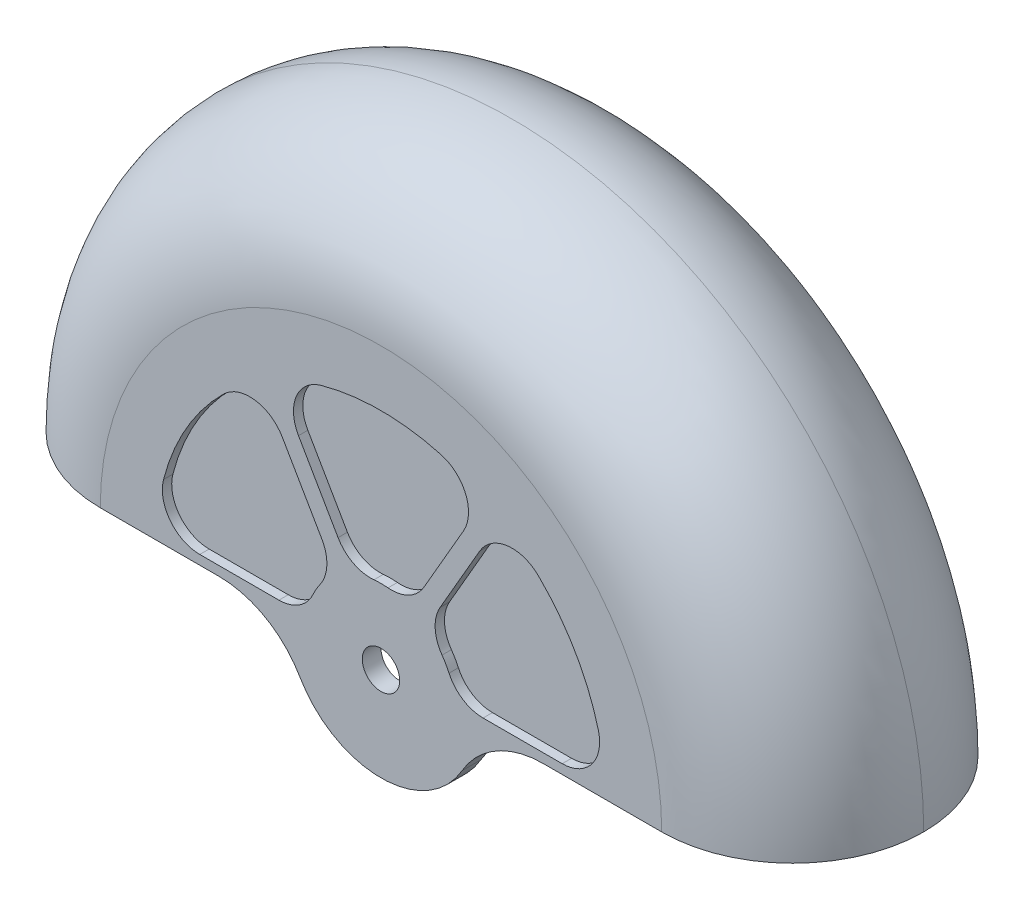
SolidWorks part; units mm, degrees
ref_plane "Front Plane" through (0, 0, 0) normal (0, 0, 1) x (1, 0, 0)
ref_plane "Top Plane" through (0, 0, 0) normal (0, 1, 0) x (1, 0, 0)
ref_plane "Right Plane" through (0, 0, 0) normal (1, 0, 0) x (0, 0, -1)
sketch "Sketch1" plane through (0, 0, 0) normal (0, 0, 1) x (1, 0, 0)
  circle A0 centre (0, 0) radius 110
  dimension "D1" = 220
extrude "Extrude1" add sketch "Sketch1" along normal blind 70
fillet "Fillet1" radius 35 2 edges at (110, 0, 0) (110, 0, 70)
sketch "Sketch2" plane through (0, 0, 0) normal (0, 0, 1) x (1, 0, 0)
  line L0 (43.3013, 0) -> (110, 0)
  line L1 (-110, 0) -> (-43.3013, 0)
  line L2 (-110, 0) -> (-110, -110)
  line L3 (-110, -110) -> (110, -110)
  line L4 (110, 0) -> (110, -110)
  arc A0 (-21.6506, -12.5) -> (21.6506, -12.5) centre (0, 0) ccw
  circle A1 centre (0, 0) radius 110 construction
  arc A2 (-43.3013, 0) -> (-21.6506, -12.5) centre (-43.3013, -25) cw
  arc A3 (43.3013, 0) -> (21.6506, -12.5) centre (43.3013, -25) ccw
  dimension "D1" = 50
  dimension "D2" = 25
extrude "Extrude2" cut sketch "Sketch2" along normal through all
shell "Shell1" thickness 5 removed face at (-72.22, 0, 35) removed face at (-31.6386, -4.7997, 35) removed face at (0, -18.75, 35) removed face at (31.6386, -4.7997, 35) removed face at (72.22, 0, 35)
sketch "Sketch3" plane through (0, 0, 70) normal (0, 0, 1) x (1, 0, 0)
  circle A0 centre (0, 0) radius 5
  dimension "D1" = 10
extrude "Extrude3" cut sketch "Sketch3" against normal through all
sketch "Sketch5" plane through (0, 0, 70) normal (0, 0, 1) x (1, 0, 0)
  line L3 (-27.2718, 2.5) -> (-48.4123, 2.5)
  line L4 (-11.4708, 24.8681) -> (-22.0411, 43.1763)
  line L5 (27.2718, 2.5) -> (48.4123, 2.5)
  line L8 (-15.801, 22.3681) -> (-26.3712, 40.6763)
  line L9 (11.4708, 24.8681) -> (22.0411, 43.1763)
  line L10 (15.801, 22.3681) -> (26.3712, 40.6763)
  arc A0 (58.0948, 15) -> (42.0378, 42.8115) centre (0, 0) ccw
  arc A1 (18.1812, 8.3333) -> (16.3075, 11.5787) centre (0, 0) ccw
  arc A2 (16.057, 57.8115) -> (-16.057, 57.8115) centre (0, 0) ccw
  arc A3 (1.8737, 19.912) -> (-1.8737, 19.912) centre (0, 0) ccw
  arc A4 (-16.3075, 11.5787) -> (-18.1812, 8.3333) centre (0, 0) ccw
  arc A5 (-27.2718, 2.5) -> (-18.1812, 8.3333) centre (-27.2718, 12.5) ccw
  arc A6 (-42.0378, 42.8115) -> (-58.0948, 15) centre (0, 0) ccw
  arc A7 (-15.801, 22.3681) -> (-16.3075, 11.5787) centre (-24.4612, 17.3681) cw
  arc A8 (-11.4708, 24.8681) -> (-1.8737, 19.912) centre (-2.8106, 29.8681) ccw
  arc A9 (11.4708, 24.8681) -> (1.8737, 19.912) centre (2.8106, 29.8681) cw
  arc A10 (-22.0411, 43.1763) -> (-16.057, 57.8115) centre (-13.3808, 48.1763) cw
  arc A11 (-42.0378, 42.8115) -> (-26.3712, 40.6763) centre (-35.0315, 35.6763) cw
  arc A12 (16.057, 57.8115) -> (22.0411, 43.1763) centre (13.3808, 48.1763) cw
  arc A13 (42.0378, 42.8115) -> (26.3712, 40.6763) centre (35.0315, 35.6763) ccw
  arc A14 (15.801, 22.3681) -> (16.3075, 11.5787) centre (24.4612, 17.3681) ccw
  arc A15 (27.2718, 2.5) -> (18.1812, 8.3333) centre (27.2718, 12.5) cw
  arc A16 (48.4123, 2.5) -> (58.0948, 15) centre (48.4123, 12.5) ccw
  arc A17 (-48.4123, 2.5) -> (-58.0948, 15) centre (-48.4123, 12.5) cw
  point P12 (-12.0866, 15.9347)
  point P13 (20, 2.5)
  point P15 (60, 2.5)
  point P23 (-7.7565, 18.4347)
  point P26 (7.7565, 18.4347)
  dimension "D1" = 120
  dimension "D2" = 40
  dimension "D3" = 10
extrude "Extrude7" cut sketch "Sketch5" against normal blind 2.5
